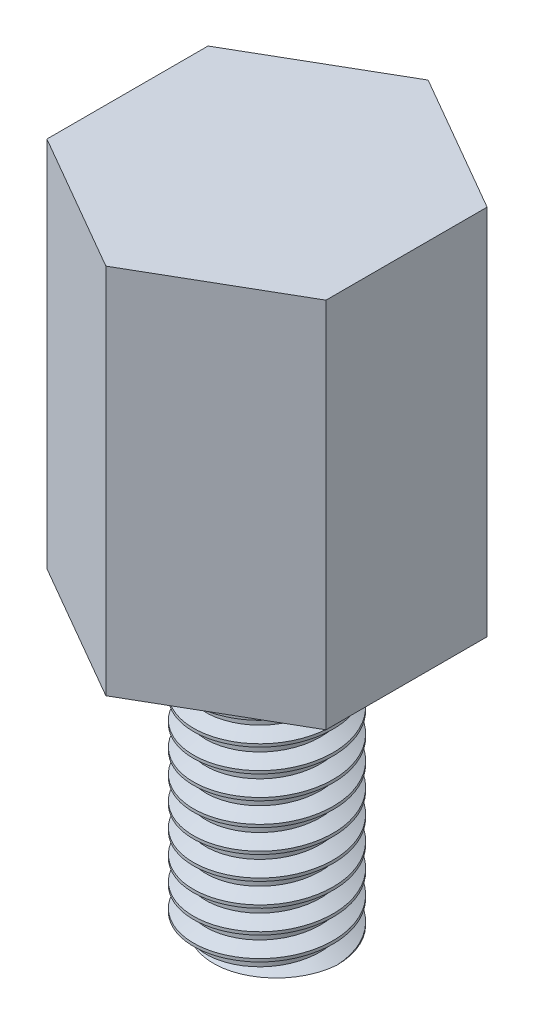
SolidWorks part; units mm, degrees
material "Brass"
ref_plane "Front Plane" through (0, 0, 0) normal (0, 0, 1) x (1, 0, 0)
ref_plane "Top Plane" through (0, 0, 0) normal (0, 1, 0) x (1, 0, 0)
ref_plane "Right Plane" through (0, 0, 0) normal (1, 0, 0) x (0, 0, -1)
sketch "Sketch1" plane through (0, 0, 0) normal (0, 1, 0) x (1, 0, 0)
  line L1 (3, 1.7321) -> (0, 3.4641)
  line L2 (0, 3.4641) -> (-3, 1.7321)
  line L3 (-3, 1.7321) -> (-3, -1.7321)
  line L4 (-3, -1.7321) -> (0, -3.4641)
  line L5 (0, -3.4641) -> (3, -1.7321)
  line L6 (3, -1.7321) -> (3, 1.7321)
  circle A0 centre (0, 0) radius 3 construction
  dimension "D1" = 6
extrude "Boss-Extrude1" add sketch "Sketch1" along normal blind 25 contours L2 L3 L4 L5 L6 L1
sketch "Sketch2" plane through (0, 0, 0) normal (0, -1, 0) x (1, 0, 0)
  circle A0 centre (0, 0) radius 1.5
  dimension "D1" = 3
extrude "Boss-Extrude2" add sketch "Sketch2" along normal blind 6
hole_wizard "Tap Drill for M3 Tap1" positions "Sketch3" profile "Sketch4" hole size "M3" standard "ISO"
sketch "Sketch3" plane through (0, 25, 0) normal (0, 1, 0) x (1, 0, 0)
  point P0 (0, 0)
sketch "Sketch4" plane through (0, 25, 0) normal (1, 0, 0) x (0, 0, 1)
  line L0 (0, 0) -> (0, 10.7511)
  line L1 (0, 10.7511) -> (1.25, 10)
  line L2 (1.25, 10) -> (1.25, 0)
  line L5 (1.25, 0) -> (0, 0)
  line L10 (0, 10.7511) -> (-1.25, 10) construction
  line L11 (0, -6.35) -> (0, 107.95) construction
  dimension "Hole Dia." = 2.5
  dimension "Hole Depth" = 10
  dimension "Drill Angle" = 118
thread "Thread1" pitch 0.5 method cut trim with start face yes profile "Thread Profile1" start angle 0, offset 1, length 9, pitch 0.5, diameter 2.5
ref_plane "Plane1" through (-1.25, 26, 0) normal (0, 0, 1) x (-1, 0, 0)
sketch "Thread Profile1" plane through (-1.25, 26, 0) normal (0, 0, 1) x (-1, 0, 0)
  line L0 (0, 0) -> (0, 0.5) construction
  line L1 (0, 0) -> (0.2706, 0.1562)
  line L2 (0.2706, 0.1562) -> (0.2706, 0.2187)
  line L3 (0.2706, 0.2187) -> (0, 0.375)
  line L4 (0.2706, 0.1875) -> (0, 0.1875) construction
  line L11 (0, 0) -> (0, 0.375)
  point P2 (0, 0)
  dimension "Pitch" = 0.5
  dimension "Profile_Angle" = 60
  dimension "Profile_Land" = 0.0625
  dimension "Profile_Height" = 0.2706
thread "Thread2" pitch 0.5 method cut profile "Thread Profile2" start angle 0, offset 1, length 6.5, pitch 0.5, diameter 3
ref_plane "Plane2" through (1.5, -7, 0) normal (0, 0, 1) x (1, 0, 0)
sketch "Thread Profile2" plane through (1.5, -7, 0) normal (0, 0, 1) x (1, 0, 0)
  line L0 (0, 0) -> (0, 0.5) construction
  line L11 (0, 0) -> (0, 0.4375)
  line L12 (0, 0.4375) -> (-0.2706, 0.2812)
  line L13 (-0.2706, 0.2812) -> (-0.2706, 0.1562)
  line L15 (-0.2706, 0.1562) -> (0, 0)
  line L17 (-0.2706, 0.2187) -> (0, 0.2187) construction
  point P2 (0, 0)
  dimension "Pitch" = 0.5
  dimension "Profile_Angle" = 60
  dimension "Profile_Land" = 0.125
  dimension "Profile_Height" = 0.2706
sketch "Sketch9" plane through (0, 0, 0) normal (0, 1, 0) x (1, 0, 0)
  circle A0 centre (0, 0) radius 1.225
  dimension "D1" = 2.45
extrude "Cut-Extrude-Thin1" cut sketch "Sketch9" against normal blind 0.5 thin contours A0 thin type one direction wall 10
ref_plane "基准面1" through (0, 8, 0) normal (0, -1, 0) x (-1, 0, 0)
sketch "草图1" plane through (0, 8, 0) normal (0, -1, 0) x (-1, 0, 0)
  line L1 (5.4472, 4.7193) -> (-5.4598, 4.7193)
  line L2 (5.4472, 4.7193) -> (5.4472, -5.4116)
  line L3 (5.4472, -5.4116) -> (-5.4598, -5.4116)
  line L4 (-5.4598, 4.7193) -> (-5.4598, -5.4116)
extrude "切除-拉伸1" cut sketch "草图1" against normal blind 25
